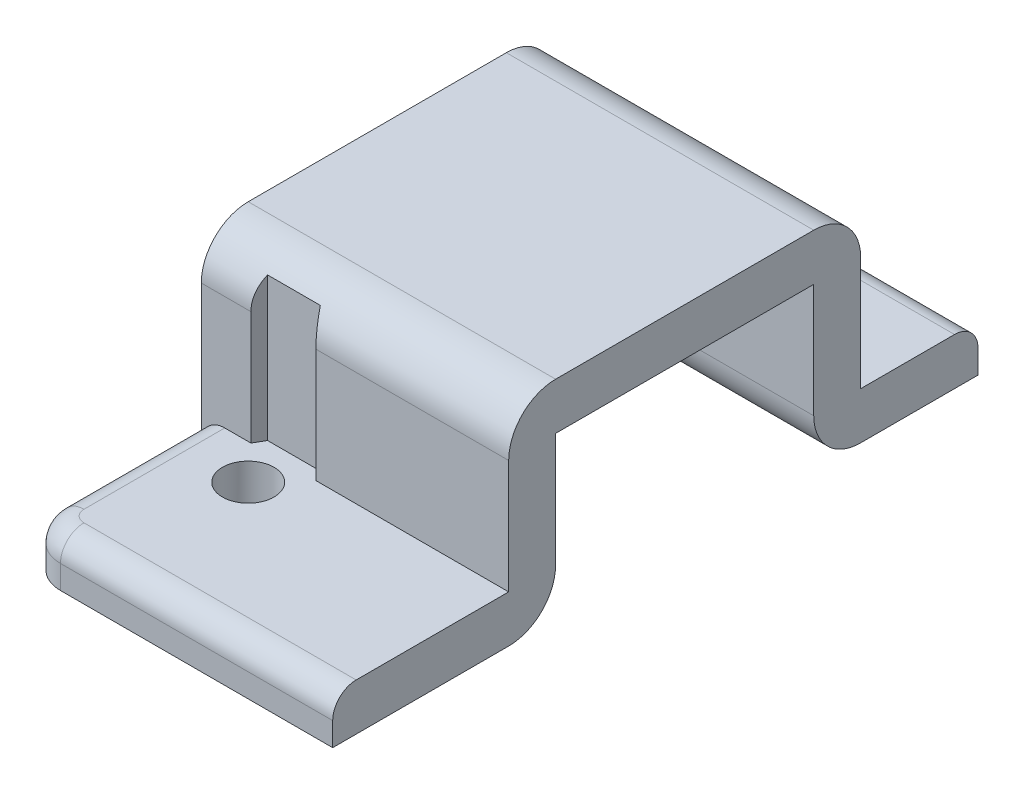
SolidWorks part; units mm, degrees
ref_plane "Front Plane" through (0, 0, 0) normal (0, 0, 1) x (1, 0, 0)
ref_plane "Top Plane" through (0, 0, 0) normal (0, 1, 0) x (1, 0, 0)
ref_plane "Right Plane" through (0, 0, 0) normal (1, 0, 0) x (0, 0, -1)
sketch "Sketch1" plane through (0, 0, 0) normal (1, 0, 0) x (0, 0, -1)
  line L0 (0, 55) -> (0, -55) construction
  line L3 (-5.5, 6.85) -> (5.5, 6.85)
  line L5 (-5.5, 8.85) -> (5.5, 6.85) construction
  line L6 (-5.5, 6.85) -> (5.5, 8.85) construction
  line L7 (55, 0) -> (-55, 0) construction
  line L9 (-5.5, 0) -> (-5.5, 6.85)
  line L10 (-7.5, 2) -> (-15, 2)
  line L11 (-15, 0) -> (-15, 2)
  line L12 (-7.5, 8.85) -> (7.5, 8.85)
  line L13 (7.5, 2) -> (12.5, 2)
  line L14 (5.5, 6.85) -> (5.5, 0)
  line L16 (12.5, 2) -> (12.5, 0)
  line L17 (-5.5, 0) -> (-15, 0)
  line L20 (-7.5, 2) -> (-7.5, 8.85)
  line L21 (5.5, 0) -> (12.5, 0)
  line L24 (7.5, 2) -> (7.5, 8.85)
  point P0 (0, 7.85)
  dimension "D1" = 9.5
  dimension "D2" = 11
  dimension "D3" = 2
  dimension "D4" = 2
  dimension "D5" = 2
  dimension "D6" = 7
  dimension "D7" = 2
  dimension "D8" = 6.85
  dimension "D9" = 2
extrude "Boss-Extrude1" add sketch "Sketch1" along normal mid plane 13.1 contours L13 L24 L20 L10 L11 L9 L3 L14 L16 region at (0, 3.425, 5.7889)
sketch "Sketch2" plane through (0, 2, 0) normal (0, 1, 0) x (1, 0, 0)
  line L1 (-6.55, -7.5) -> (-6.55, -15) construction
  line L2 (6.55, -15) -> (-6.55, -15) construction
  circle A0 centre (-3.05, -9) radius 1.1
  dimension "D3" = 2.2
  dimension "D1" = 3.5
  dimension "D2" = 6
extrude "Cut-Extrude1" cut sketch "Sketch2" against normal up to next
sketch "Sketch3" plane through (0, 2, 0) normal (0, 1, 0) x (1, 0, 0)
  line L1 (-5.3, -9) -> (-4.175, -10.9486)
  line L2 (-4.175, -10.9486) -> (-1.925, -10.9486)
  line L3 (-1.925, -10.9486) -> (-0.8, -9)
  line L4 (-0.8, -9) -> (-1.925, -7.0514)
  line L5 (-1.925, -7.0514) -> (-4.175, -7.0514)
  line L6 (-4.175, -7.0514) -> (-5.3, -9)
  line L9 (6.55, -15) -> (-6.55, -15) construction
  circle A0 centre (-3.05, -9) radius 2.25 construction
  circle A1 centre (-3.05, -9) radius 1.9486 construction
  dimension "D1" = 4.5
extrude "Cut-Extrude2" cut sketch "Sketch3" along normal up to next
mirror "Mirror1" about plane through (0, 0, 0) normal (0, 0, 1) of "Cut-Extrude2", "Cut-Extrude1"
fillet "Fillet1" radius 2 4 edges at (0, 0, -5.5) (0, 0, 5.5) (2.442, 8.85, 7.5) (2.442, 8.85, -7.5)
fillet "Fillet3" radius 1.5 2 edges at (-6.55, 1, 15) (-6.55, 1, -12.5)
fillet "Fillet4" radius 1 6 edges at (-6.55, 2, 10.5) (-6.1107, 2, 14.5607) (-6.55, 2, -9.25) (-6.1107, 2, -12.0607) (0.75, 2, 15) (0.75, 2, -12.5)
